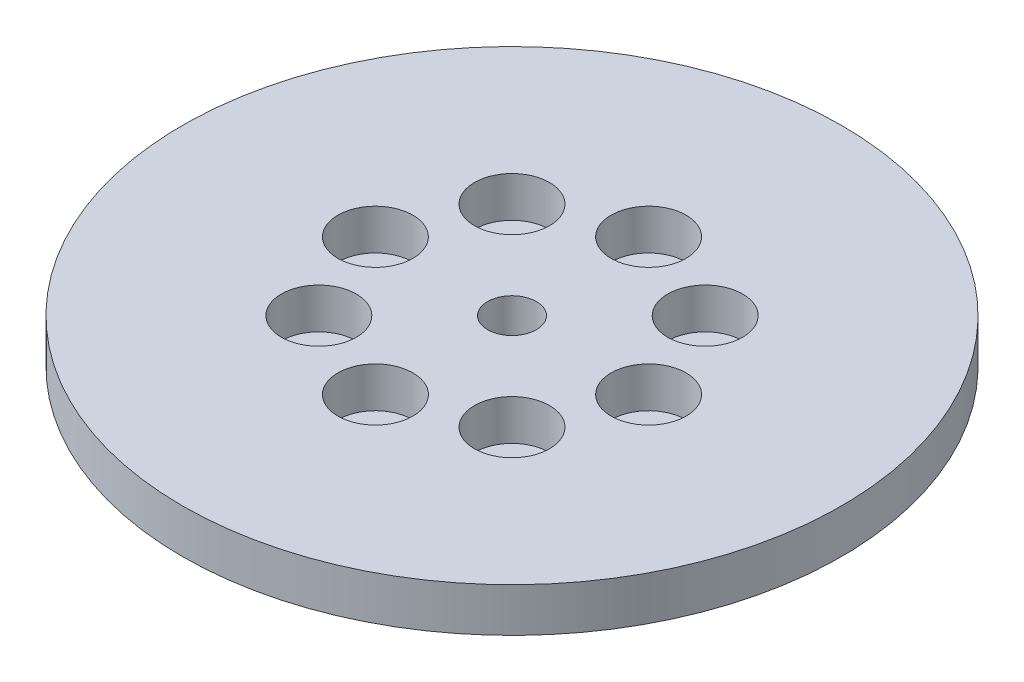
SolidWorks part; units mm, degrees
ref_plane "Front Plane" through (0, 0, 0) normal (0, 0, 1) x (1, 0, 0)
ref_plane "Top Plane" through (0, 0, 0) normal (0, 1, 0) x (1, 0, 0)
ref_plane "Right Plane" through (0, 0, 0) normal (1, 0, 0) x (0, 0, -1)
sketch "Sketch1" plane through (0, 0, 0) normal (0, 1, 0) x (1, 0, 0)
  circle A0 centre (0, 0) radius 67.5
  dimension "FLANGE_OD" = 135
extrude "Boss-Extrude1" add sketch "Sketch1" along normal blind 9
sketch "Sketch2" plane through (0, 0, 0) normal (0, 1, 0) x (1, 0, 0)
  circle A0 centre (0, 0) radius 5
  dimension "BORE_D" = 10
extrude "Cut-Extrude1" cut sketch "Sketch2" along normal through all
sketch "Sketch3" plane through (0, 9, 0) normal (0, 1, 0) x (1, 0, 0)
  circle A0 centre (0, 0) radius 27.9777 construction
  circle A1 centre (-27.9777, 0) radius 7.6776
  dimension "BOLT_D" = 15.3552
  dimension "BOLT_PCD" = 55.9554
extrude "Cut-Extrude2" cut sketch "Sketch3" against normal blind 8.3051
pattern_circular "CirPattern1" count 8 over 360 about axis through (0, 0, 0) along (0, 1, 0) of "Cut-Extrude2"
